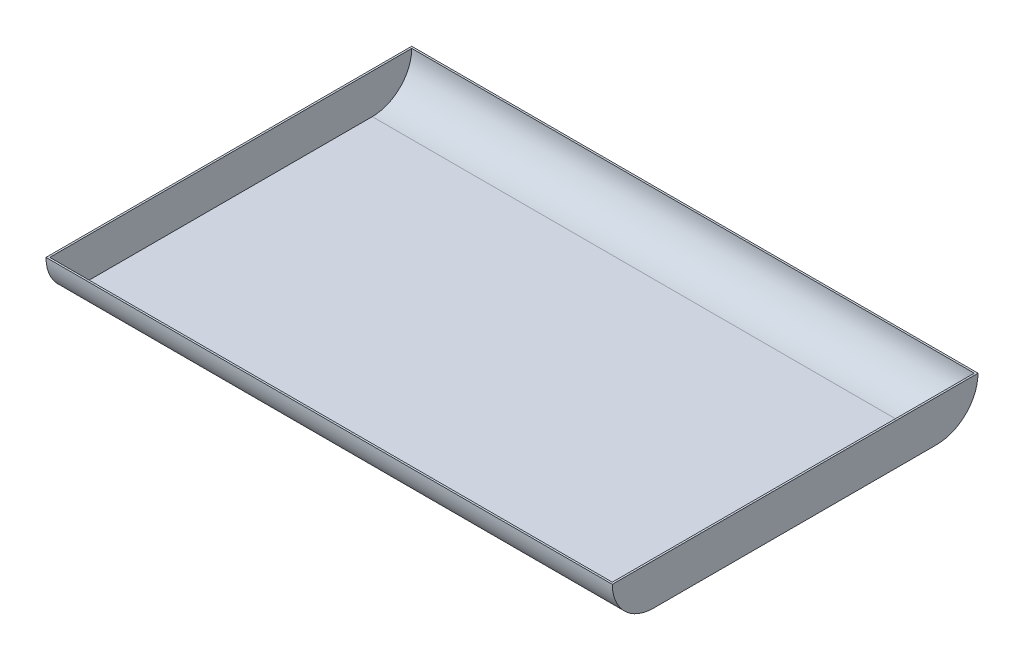
SolidWorks part; units mm, degrees
ref_plane "Front Plane" through (0, 0, 0) normal (0, 0, 1) x (1, 0, 0)
ref_plane "Top Plane" through (0, 0, 0) normal (0, 1, 0) x (1, 0, 0)
ref_plane "Right Plane" through (0, 0, 0) normal (1, 0, 0) x (0, 0, -1)
sketch "Sketch1" plane through (0, 0, 0) normal (1, 0, 0) x (0, 0, -1)
  line L0 (-152.4, 0) -> (152.4, 0)
  line L1 (-196.85, 44.45) -> (196.85, 44.45)
  line L2 (0, 0) -> (0, 113.2403) construction
  arc A0 (-152.4, 0) -> (-196.85, 44.45) centre (-152.4, 44.45) cw
  arc A1 (152.4, 0) -> (196.85, 44.45) centre (152.4, 44.45) ccw
  point P9 (0, 44.45)
  dimension "D3" = 44.45
  dimension "D1" = 304.8
  dimension "D2" = 152.4
extrude "CoverBaseExtrude" add sketch "Sketch1" along normal blind 304.8 and the other way blind 304.8 contours L1 A1 L0 A0
shell "CoverShell" thickness 2 removed face at (0, 44.45, 0)
